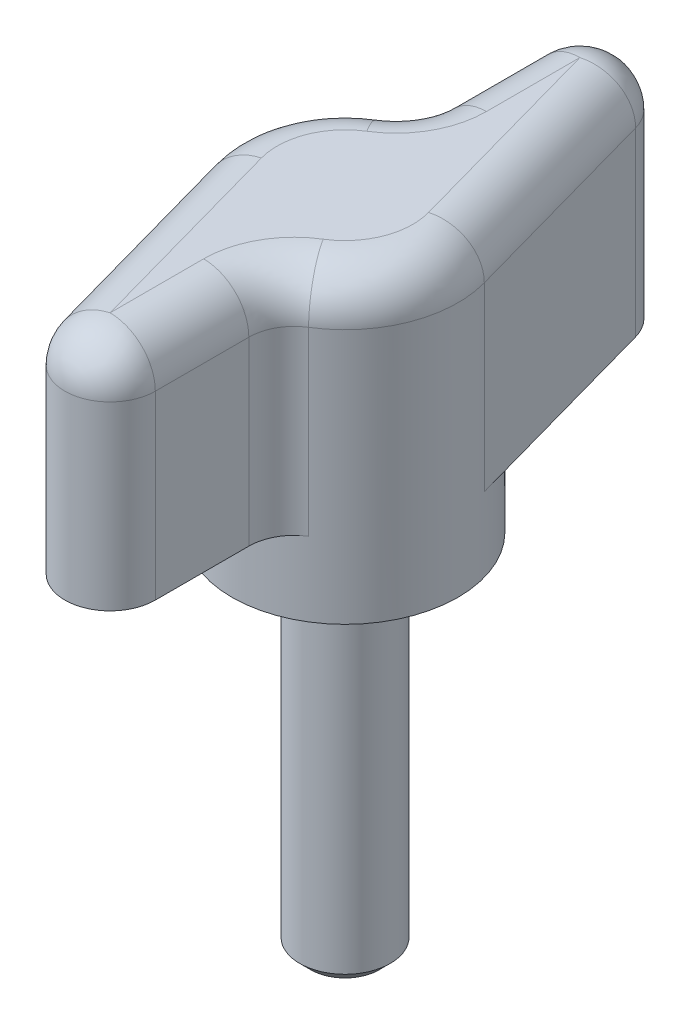
SolidWorks part; units mm, degrees
ref_plane "Front" through (0, 0, 0) normal (0, 0, 1) x (1, 0, 0)
ref_plane "Top" through (0, 0, 0) normal (0, 1, 0) x (1, 0, 0)
ref_plane "Right" through (0, 0, 0) normal (1, 0, 0) x (0, 0, -1)
sketch "Sketch1" plane through (0, 0, 0) normal (0, 1, 0) x (1, 0, 0)
  circle A0 centre (0, 0) radius 7.9375
  dimension "D1" = 15.875
extrude "Extrude1" add sketch "Sketch1" along normal blind 21.082
sketch "Sketch2" plane through (0, 21.082, 0) normal (0, 1, 0) x (-1, 0, 0)
  line L0 (2.6895, -16.002) -> (2.6895, -7.468)
  line L1 (-3.544, -16.8541) -> (-7.6463, -2.1304)
  arc A0 (-3.544, -16.8541) -> (2.6895, -16.002) centre (-0.4855, -16.002) ccw
  circle A1 centre (0, 0) radius 7.9375 construction
  arc A2 (-7.6463, -2.1304) -> (2.6895, -7.468) centre (0, 0) ccw
  dimension "D1" = 16.002
  dimension "D2" = 3.175
  dimension "D3" = 3.175
  dimension "D4" = 13.8716
extrude "Extrude2" add sketch "Sketch2" against normal blind 15.875
ref_axis "Axis2" through (0, 17.907, 0) along (0, -1, 0)
pattern_circular "CirPattern4" count 2 every 180 about axis through (0, 17.907, 0) along (0, -1, 0) of "Extrude2"
fillet "Fillet1" radius 3.175 10 edges at (-2.6895, 21.082, -11.735) (0.0554, 21.082, -19.1477) (5.5951, 21.082, -9.4923) (7.0526, 21.082, 3.6421) (2.6895, 21.082, 11.735) (-0.0554, 21.082, 19.1477) (-5.5951, 21.082, 9.4923) (-7.0526, 21.082, -3.6421) (2.6895, 13.1445, 7.468) (-2.6895, 13.1445, -7.468)
sketch "Sketch7" plane through (0, 0, 0) normal (0, -1, 0) x (1, 0, 0)
  circle A0 centre (0, 0) radius 3.175
  dimension "D1" = 6.35
extrude "Extrude3" add sketch "Sketch7" along normal blind 25.4 separate body
chamfer "Chamfer1" distance 0.762 angle 45 1 edges at (0, -25.4, -3.175)
